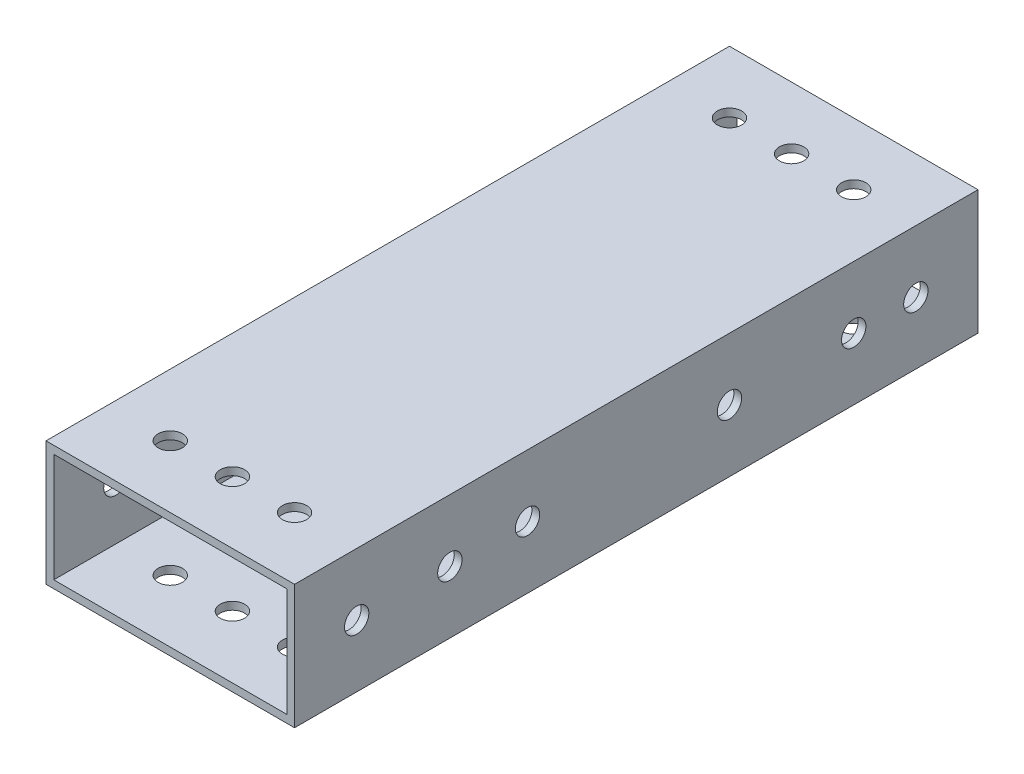
SolidWorks part; units mm, degrees
material "6061-T6 (SS)"
ref_plane "Front Plane" through (0, 0, 0) normal (0, 0, 1) x (1, 0, 0)
ref_plane "Top Plane" through (0, 0, 0) normal (0, 1, 0) x (1, 0, 0)
ref_plane "Right Plane" through (0, 0, 0) normal (1, 0, 0) x (0, 0, -1)
sketch "Sketch1" plane through (0, 0, 0) normal (0, 0, 1) x (1, 0, 0)
  line L0 (-23.8125, 11.1125) -> (23.8125, 11.1125)
  line L1 (-25.4, -12.7) -> (25.4, -12.7)
  line L2 (-25.4, -12.7) -> (-25.4, 12.7)
  line L3 (-25.4, 12.7) -> (25.4, 12.7)
  line L4 (25.4, -12.7) -> (25.4, 12.7)
  line L5 (-25.4, -12.7) -> (25.4, 12.7) construction
  line L6 (-25.4, 12.7) -> (25.4, -12.7) construction
  line L7 (23.8125, -11.1125) -> (23.8125, 11.1125)
  line L8 (-23.8125, -11.1125) -> (23.8125, -11.1125)
  line L9 (-23.8125, -11.1125) -> (-23.8125, 11.1125)
  point P0 (0, 0)
  dimension "D1" = 50.8
  dimension "D2" = 25.4
  dimension "D3" = 1.5875
extrude "Boss-Extrude1" add sketch "Sketch1" along normal mid plane 139.7
sketch "Sketch2" plane through (0, 12.7, 0) normal (0, 1, 0) x (1, 0, 0)
  line L0 (25.4, 69.85) -> (-25.4, 69.85) construction
  line L1 (25.4, 0) -> (-25.4, 0) construction
  line L2 (25.4, -69.85) -> (25.4, 69.85) construction
  line L3 (-25.4, -69.85) -> (-25.4, 69.85) construction
  circle A0 centre (-12.7, 57.15) radius 2.4892
  circle A1 centre (0, 57.15) radius 2.4892
  circle A2 centre (12.7, 57.15) radius 2.4892
  circle A3 centre (12.7, -57.15) radius 2.4892
  circle A4 centre (0, -57.15) radius 2.4892
  circle A5 centre (-12.7, -57.15) radius 2.4892
  dimension "D1" = 4.9784
  dimension "D2" = 12.7
  dimension "D3" = 12.7
  dimension "D4" = 12.7
extrude "Cut-Extrude1" cut sketch "Sketch2" against normal through all
sketch "Sketch3" plane through (25.4, 0, 0) normal (1, 0, 0) x (0, 0, -1)
  line L0 (0, 12.7) -> (0, -12.7) construction
  line L1 (-69.85, 12.7) -> (69.85, 12.7) construction
  line L2 (-69.85, -12.7) -> (69.85, -12.7) construction
  line L3 (-69.85, -12.7) -> (-69.85, 12.7) construction
  line L5 (69.85, -12.7) -> (69.85, 12.7) construction
  circle A8 centre (57.15, 0) radius 2.4892
  circle A9 centre (44.45, 0) radius 2.4892
  circle A10 centre (19.05, 0) radius 2.4892
  circle A11 centre (-57.15, 0) radius 2.4892
  circle A14 centre (-38.1, 0) radius 2.4892
  circle A15 centre (-22.225, 0) radius 2.4892
  dimension "D1" = 12.7
  dimension "D3" = 15.875
  dimension "D8" = 4.9784
  dimension "D2" = 31.75
  dimension "D4" = 25.4
  dimension "D7" = 25.4
extrude "Cut-Extrude2" cut sketch "Sketch3" against normal through all
